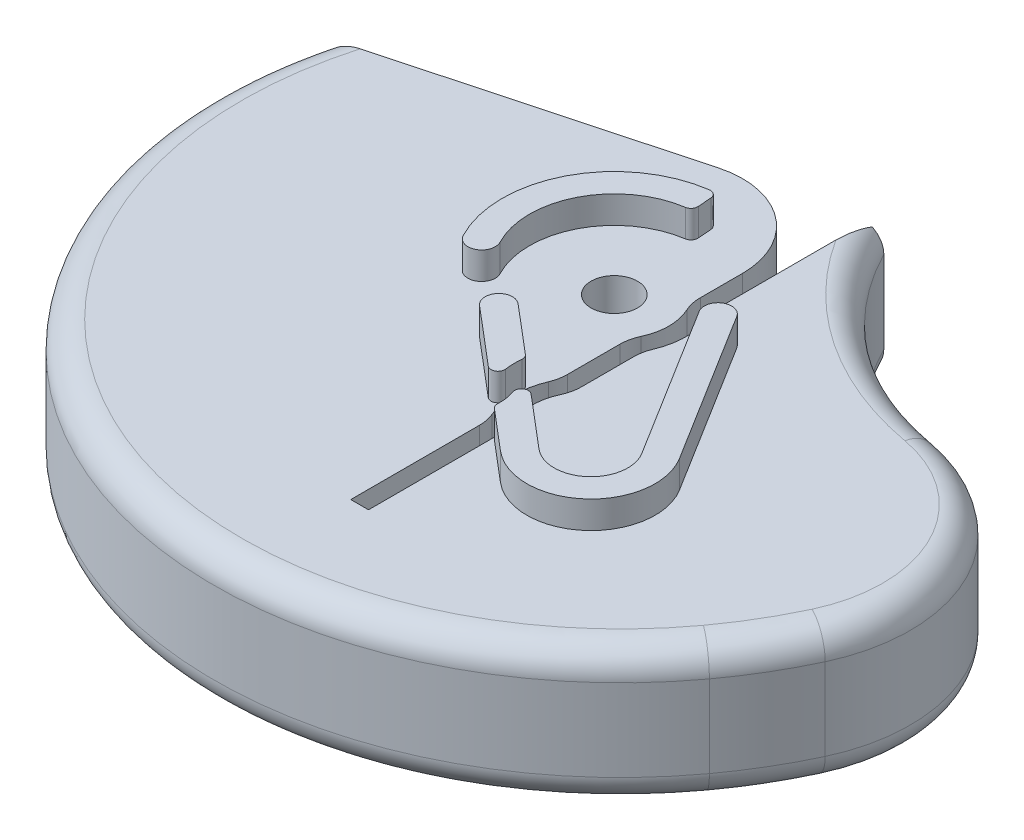
SolidWorks part; units mm, degrees
ref_plane "Front Plane" through (0, 0, 0) normal (0, 0, 1) x (1, 0, 0)
ref_plane "Top Plane" through (0, 0, 0) normal (0, 1, 0) x (1, 0, 0)
ref_plane "Right Plane" through (0, 0, 0) normal (1, 0, 0) x (0, 0, -1)
sketch "Sketch1" plane through (0, 0, 0) normal (0, 1, 0) x (1, 0, 0)
  line L0 (0, 0) -> (0, 29) construction
  line L1 (0, 0) -> (-29, 0) construction
  line L2 (-29, 3) -> (-24, 3)
  line L3 (-3, 29) -> (-3, 24)
  line L4 (0, 29) -> (-3, 29)
  line L5 (-29, 0) -> (-29, 3)
  line L6 (3, 29) -> (3, 24)
  line L7 (0, 29) -> (3, 29)
  line L8 (29, 3) -> (24, 3)
  line L9 (29, 0) -> (29, 3)
  line L10 (29, -3) -> (24, -3)
  line L11 (29, 0) -> (29, -3)
  line L12 (3, -29) -> (3, -24)
  line L13 (0, -29) -> (3, -29)
  line L14 (-3, -29) -> (-3, -24)
  line L15 (0, -29) -> (-3, -29)
  line L16 (-29, -3) -> (-24, -3)
  line L17 (-29, 0) -> (-29, -3)
  circle A0 centre (-24, 24) radius 20 construction
  circle A1 centre (-24, 24) radius 21 construction
  arc A2 (-3, 24) -> (-24, 3) centre (-24, 24) cw
  arc A3 (24, 3) -> (3, 24) centre (24, 24) cw
  arc A4 (3, -24) -> (24, -3) centre (24, -24) cw
  arc A5 (-24, -3) -> (-3, -24) centre (-24, -24) cw
  point P37 (0, 0)
  dimension "D1" = 40
  dimension "D4" = 5
  dimension "D6" = 1
  dimension "D7" = 29
  dimension "D8" = 4
  dimension "D2" = 24
  dimension "D3" = 24
  dimension "D5" = 5
extrude "Boss-Extrude1" add sketch "Sketch1" along normal blind 10
sketch "Sketch9" plane through (0, 10, 0) normal (0, 1, 0) x (1, 0, 0)
  line L0 (-3, -29) -> (3, -29) construction
  line L1 (-4.201, -31) -> (3, -31)
  line L2 (3, -31) -> (3, -29)
  line L4 (-3, -24) -> (-3, -29) construction
  line L5 (-3, -29) -> (3, -29)
  line L6 (-3, -24) -> (-3, -29)
  line L7 (-31, -3) -> (-29, -3)
  line L8 (-29, 3) -> (-29, -3)
  line L9 (-24, 3) -> (-29, 3)
  line L10 (-31, 4.201) -> (-31, -3)
  line L11 (-3, 31) -> (-3, 29)
  line L12 (3, 29) -> (-3, 29)
  line L13 (3, 24) -> (3, 29)
  line L14 (4.201, 31) -> (-3, 31)
  line L15 (31, 3) -> (29, 3)
  line L16 (29, -3) -> (29, 3)
  line L17 (24, -3) -> (29, -3)
  line L18 (31, -4.201) -> (31, 3)
  arc A0 (-3, -24) -> (-24, -3) centre (-24, -24) ccw construction
  arc A1 (-4.201, -31) -> (-3, -24) centre (-24, -24) ccw
  arc A2 (-31, 4.201) -> (-24, 3) centre (-24, 24) ccw
  arc A3 (4.201, 31) -> (3, 24) centre (24, 24) ccw
  arc A4 (31, -4.201) -> (24, -3) centre (24, -24) ccw
  point P28 (0, 0)
  dimension "D1" = 2
extrude "Boss-Extrude8" add sketch "Sketch9" against normal up to surface (10 mm away) up to face at (0, 0, 0)
sketch "Sketch15" plane through (0, 0, 0) normal (0, -1, 0) x (1, 0, 0)
  line L0 (31, -3) -> (24, -3) construction
  line L1 (31, -3) -> (24, -3)
  line L6 (31, -3) -> (31.8591, -3)
  line L7 (4.201, -31) -> (4.4449, -31.6898)
  line L8 (2.0492, -35.1342) -> (1.8017, -35.9044)
  arc A11 (31.8591, -3) -> (4.4449, -31.6898) centre (0, 0) ccw
  arc A12 (24, -3) -> (4.201, -31) centre (24, -24) ccw
  arc A13 (24, -3) -> (4.201, -31) centre (24, -24) ccw construction
  dimension "D1" = 64
extrude "Boss-Extrude11" add sketch "Sketch15" against normal up to surface (10 mm away) contours L1 A12 L7 A11 L6 up to face at (0, 10, 0)
sketch "Sketch10" plane through (0, 10, 0) normal (0, 1, 0) x (1, 0, 0)
  circle A0 centre (0, 0) radius 1.7
  dimension "D1" = 3.4
extrude "Cut-Extrude1" cut sketch "Sketch10" against normal through all
sketch "Sketch13" plane through (0, 0, 0) normal (0, -1, 0) x (1, 0, 0)
  circle A0 centre (0, 0) radius 3.5
  dimension "D1" = 7
extrude "Cut-Extrude2" cut sketch "Sketch13" against normal blind 5
fillet "Fillet11" radius 12 1 edges at (31.8591, 5, -3)
fillet "Fillet1" radius 2 6 edges at (-28.1281, 10, 15.2581) (-28.1281, 0, 15.2581) (5.8373, 10, -13.4588) (28.7772, 10, 2.961) (5.8373, 0, -13.4588) (28.7772, 0, 2.961)
sketch "Sketch19" plane through (0, 0, 0) normal (0, -1, 0) x (1, 0, 0)
  line L0 (4.201, -31) -> (4.4449, -31.6898) construction
  line L5 (4.201, -31) -> (4.4449, -31.6898)
  line L7 (-9.5394, -3) -> (-17.8496, -3) construction
  line L9 (0, -27.5) -> (3.2937, -27.5)
  arc A1 (28.9876, 13.5543) -> (4.4449, -31.6898) centre (0, 0) ccw construction
  arc A2 (-22.204, -16.2245) -> (0, -27.5) centre (0, 0) ccw
  arc A3 (25.8373, 18.8794) -> (-22.204, -16.2245) centre (1.8167, 1.3275) ccw
  arc A4 (28.9876, 13.5543) -> (4.4449, -31.6898) centre (0, 0) ccw construction
  arc A6 (25.8373, 18.8794) -> (4.4449, -31.6898) centre (0, 0) ccw
  arc A7 (20.2564, -3.3364) -> (4.201, -31) centre (24, -24) ccw construction
  arc A10 (3.2937, -27.5) -> (4.201, -31) centre (24, -24) ccw
  dimension "D2" = 55
extrude "Cut-Extrude5" cut sketch "Sketch19" against normal through all contours A2 L9 A10 L5 A6 A3
sketch "Sketch21" plane through (0, 10, 0) normal (0, 1, 0) x (1, 0, 0)
  line L0 (3.35, -2.1857) -> (3.35, -7.4569)
  line L1 (4.65, 24.87) -> (3.35, 24.87)
  line L2 (4.65, 24.87) -> (4.65, 2.5431)
  line L3 (4.65, -22.632) -> (3.35, -22.632)
  line L4 (3.35, 24.87) -> (3.35, 2.1857)
  line L5 (4.65, 24.87) -> (3.35, -22.632) construction
  line L6 (4.65, -22.632) -> (3.35, 24.87) construction
  line L7 (4.65, -2.5431) -> (4.65, -7.8143)
  line L8 (4.65, -12.1857) -> (4.65, -22.632)
  line L9 (3.35, -12.5431) -> (3.35, -22.632)
  arc A0 (3.35, -2.1857) -> (3.35, 2.1857) centre (0, 0) ccw
  arc A2 (4.65, -2.5431) -> (4.65, 2.5431) centre (0, 0) ccw
  arc A3 (4.65, -7.8143) -> (4.65, -12.1857) centre (8, -10) ccw
  arc A5 (3.35, -7.4569) -> (3.35, -12.5431) centre (8, -10) ccw
  point P0 (4, 1.119)
  dimension "D3" = 8
  dimension "D4" = 1.3
  dimension "D5" = 8
  dimension "D6" = 1.3
  dimension "D1" = 1.3
  dimension "D2" = 4
  dimension "D7" = 4
  dimension "D8" = 10
extrude "Cut-Extrude6" cut sketch "Sketch21" against normal blind 8
fillet "Fillet12" radius 3 8 edges at (4.65, 6, -2.5431) (4.65, 6, 2.5431) (4.65, 6, 7.8143) (4.65, 6, 12.1857) (3.35, 6, 12.5431) (3.35, 6, 7.4569) (3.35, 6, 2.1857) (3.35, 6, -2.1857)
sketch "Sketch23" plane through (0, 10, 0) normal (0, 1, 0) x (1, 0, 0)
  line L5 (-35.2086, 3.4964) -> (-29.0216, 30.4643)
  line L10 (4.7742, 30.4643) -> (-29.0216, 30.4643)
  line L11 (-35.2086, 3.4964) -> (11.6359, 16.1015)
  line L13 (11.6359, 16.1015) -> (4.7742, 30.4643)
  point P0 (-29.0216, 30.4643)
sketch "Sketch22" plane through (0, 10, 0) normal (0, 1, 0) x (1, 0, 0)
  line L0 (-0.8118, -5.9448) -> (9.1692, -14.3956) construction
  line L1 (12.9074, -11.1672) -> (5.9997, -0.0623) construction
  line L2 (-0.8118, -5.9448) -> (9.1692, -14.3956) construction
  line L3 (12.9074, -11.1672) -> (5.9997, -0.0623) construction
  line L4 (-0.941, -6.0975) -> (2.7565, -9.2281)
  line L5 (13.0772, -11.0616) -> (6.1695, 0.0433)
  line L6 (-2.2334, -7.6238) -> (3.1713, -12.2)
  line L7 (14.7755, -10.0052) -> (7.8677, 1.0997)
  line L8 (4.0105, -10.2899) -> (9.0399, -14.5483)
  line L9 (-0.941, -6.0975) -> (9.0399, -14.5483) construction
  line L10 (4.65, -22.632) -> (4.65, -12.9458) construction
  line L11 (4.65, -13.452) -> (4.65, -12.9458)
  line L12 (4.65, -13.452) -> (7.7475, -16.0746)
  line L13 (-2.2334, -7.6238) -> (7.7475, -16.0746) construction
  line L18 (0.1757, -0.1375) -> (-5.5006, -2.8608) construction
  line L19 (0, 0) -> (-5.4097, -2.5953) construction
  line L20 (0, 0) -> (1.2221, 5.8742) construction
  line L21 (0.1757, -0.1375) -> (1.458, 6.0261) construction
  line L22 (-0.4741, 6.1818) -> (-0.627, 8.176)
  arc A1 (9.1692, -14.3956) -> (12.9074, -11.1672) centre (10.7846, -12.4877) ccw construction
  arc A2 (9.1692, -14.3956) -> (12.9074, -11.1672) centre (10.7846, -12.4877) ccw construction
  arc A3 (9.0399, -14.5483) -> (13.0772, -11.0616) centre (10.7846, -12.4877) ccw
  arc A4 (7.7475, -16.0746) -> (14.7755, -10.0052) centre (10.7846, -12.4877) ccw
  arc A5 (-0.941, -6.0975) -> (-2.2334, -7.6238) centre (-1.5872, -6.8606) ccw
  arc A6 (6.1695, 0.0433) -> (7.8677, 1.0997) centre (7.0186, 0.5715) cw
  arc A7 (3.35, -13.2199) -> (3.1151, -12.0561) centre (0.35, -13.2199) ccw construction
  arc A8 (4.65, -12.9458) -> (4.3714, -11.6833) centre (1.65, -12.9458) ccw construction
  arc A9 (3.1151, -7.9439) -> (3.1151, -12.0561) centre (8, -10) ccw construction
  arc A10 (4.3714, -8.3167) -> (4.3714, -11.6833) centre (8, -10) ccw construction
  arc A11 (3.1713, -12.2) -> (3.1151, -12.0561) centre (0.35, -13.2199) ccw
  arc A12 (4.65, -12.9458) -> (4.3714, -11.6833) centre (1.65, -12.9458) ccw
  arc A13 (2.7565, -9.2281) -> (3.1151, -12.0561) centre (8, -10) ccw
  arc A14 (4.0105, -10.2899) -> (4.3714, -11.6833) centre (8, -10) ccw
  arc A16 (1.2221, 5.8742) -> (-5.4097, -2.5953) centre (0, 0) ccw construction
  arc A17 (-0.4741, 6.1818) -> (-5.5006, -2.8608) centre (0, 0) ccw
  arc A18 (-0.627, 8.176) -> (-7.2749, -3.7836) centre (0, 0) ccw
  arc A20 (-5.5006, -2.8608) -> (-7.2749, -3.7836) centre (-6.3877, -3.3222) cw
  arc A23 (1.9283, 7.97) -> (-7.2749, -3.7836) centre (0, 0) ccw construction
  arc A24 (1.458, 6.0261) -> (-5.5006, -2.8608) centre (0, 0) ccw construction
  dimension "D1" = 0.2
  dimension "D2" = 2
  dimension "D3" = 0.2
  dimension "D4" = 2
extrude "Boss-Extrude12" add sketch "Sketch22" along normal blind 2
fillet "Fillet16" radius 0.5 6 edges at (4.65, 11, 13.452) (4.0105, 11, 10.2899) (3.1713, 11, 12.2) (2.7565, 11, 9.2281) (-0.4741, 11, -6.1818) (-0.627, 11, -8.176)
extrude "Cut-Extrude8" cut sketch "Sketch23" against normal blind 10
fillet "Fillet22" radius 6 1 edges at (3.35, 6, -13.8719)
fillet "Fillet23" radius 2 2 edges at (-25.7228, 0, 12.5808) (-25.7228, 10, 12.5808)
